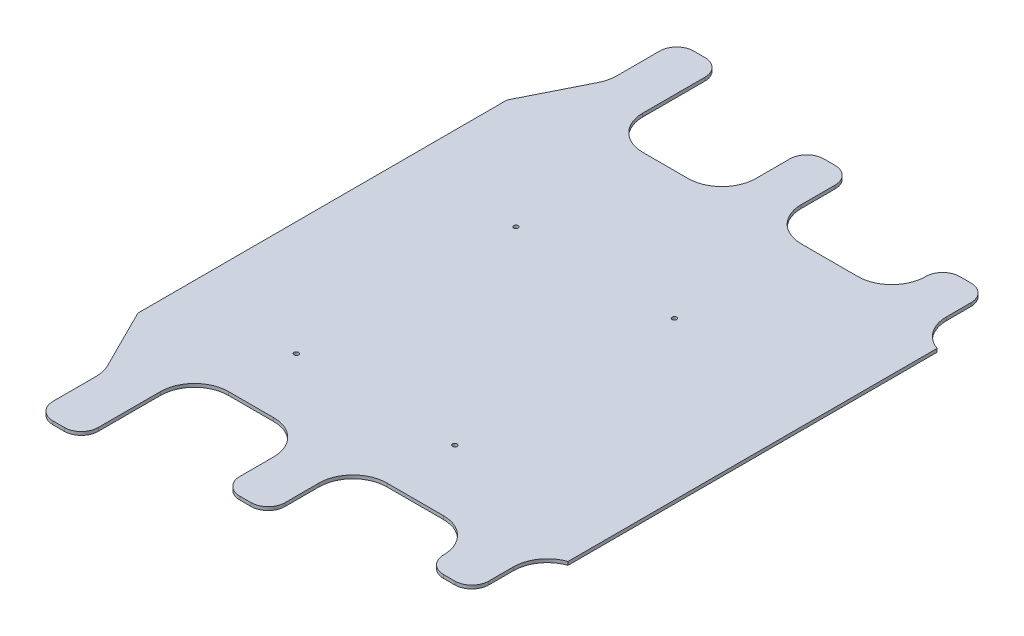
SolidWorks part; units mm, degrees
ref_plane "Front Plane" through (0, 0, 0) normal (0, 0, 1) x (1, 0, 0)
ref_plane "Top Plane" through (0, 0, 0) normal (0, 1, 0) x (1, 0, 0)
ref_plane "Right Plane" through (0, 0, 0) normal (1, 0, 0) x (0, 0, -1)
sketch "Sketch1" plane through (0, 0, 0) normal (0, 1, 0) x (1, 0, 0)
  line L1 (190, -163) -> (-190, -163)
  line L2 (190, -163) -> (190, 163)
  line L3 (190, 163) -> (-190, 163)
  line L4 (-190, -163) -> (-190, 163)
  line L5 (190, -163) -> (-190, 163) construction
  line L6 (190, 163) -> (-190, -163) construction
  point P0 (0, 0)
  dimension "D1" = 380
  dimension "D2" = 326
extrude "Boss-Extrude1" add sketch "Sketch1" along normal blind 3
sketch "Sketch2" plane through (0, 3, 0) normal (0, 1, 0) x (1, 0, 0)
  line L1 (67, -160) -> (67, 90) construction
  line L2 (67, 86) -> (-190, 86) construction
  circle A2 centre (51, 70) radius 2
  circle A4 centre (-89, 70) radius 2
  circle A5 centre (51, -124) radius 2
  circle A6 centre (-89, -124) radius 2
  dimension "D1" = 4
  dimension "D2" = 16
  dimension "D3" = 16
  dimension "D4" = 140
  dimension "D5" = 4
  dimension "D6" = 4
  dimension "D7" = 194
  dimension "D8" = 4
extrude "PCB Plate Holes" cut sketch "Sketch2" against normal up to surface (3 mm away) contours A4 | A2 | A5 | A6 up to face at (0, 0, 0)
sketch "Sketch3" plane through (0, 3, 0) normal (0, 1, 0) x (1, 0, 0)
  line L0 (190, 163) -> (-190, 163) construction
  line L5 (-190, 163) -> (-190, -163) construction
  line L7 (170, 163) -> (170, 228)
  line L11 (20, 163) -> (-20, 163)
  line L12 (130, 163) -> (170, 163)
  line L14 (170, 163) -> (170, 228)
  line L16 (190, -163) -> (190, 163) construction
  line L17 (170, 228) -> (130, 228)
  line L18 (130, 228) -> (130, 163)
  line L19 (-1.65, 0) -> (1.65, 0) construction
  line L20 (170, -228) -> (130, -228)
  line L21 (130, -228) -> (130, -163)
  line L22 (130, -163) -> (170, -163)
  line L23 (170, -163) -> (170, -228)
  line L24 (20, 163) -> (20, 258)
  line L25 (20, 258) -> (-20, 258)
  line L26 (-20, 163) -> (-20, 258)
  line L27 (-120, 163) -> (-160, 163)
  line L28 (-120, 163) -> (-120, 283)
  line L29 (-120, 283) -> (-160, 283)
  line L30 (-160, 163) -> (-160, 283)
  line L31 (-120, 183) -> (130, 183)
  line L32 (-120, -163) -> (-160, -163)
  line L33 (-160, -163) -> (-160, -283)
  line L34 (-120, -283) -> (-160, -283)
  line L35 (-120, -163) -> (-120, -283)
  line L36 (20, -163) -> (-20, -163)
  line L37 (-20, -163) -> (-20, -258)
  line L38 (20, -258) -> (-20, -258)
  line L39 (20, -163) -> (20, -258)
  line L40 (-120, -183) -> (130, -183)
  line L41 (-190, 163) -> (-160, 223)
  line L42 (-190, -163) -> (-160, -223)
  line L43 (170, 166) -> (190, 166)
  line L44 (190, 163) -> (190, 166)
  line L45 (-160, -283) -> (-160, -163)
  line L46 (190, -163) -> (190, -166)
  line L47 (170, -166) -> (190, -166)
  point P30 (130, 195.5)
  dimension "D2" = 20
  dimension "D3" = 3
  dimension "D1" = 20
  dimension "D4" = 65
  dimension "D5" = 30
  dimension "D6" = 40
  dimension "D7" = 110
  dimension "D8" = 40
  dimension "D9" = 40
  dimension "D10" = 120
  dimension "D11" = 95
extrude "Boss-Extrude2" add sketch "Sketch3" against normal up to surface (3 mm away) from surface at 0 up to face at (-89, 0, 126) starting at face at (-89, 3, 126)
sketch "Sketch5" plane through (0, 0, 0) normal (0, -1, 0) x (1, 0, 0)
  line L0 (190, -146.9564) -> (-165.4716, -212.0568)
  line L3 (-160, 272.0526) -> (170, 211.617)
  line L4 (-160, -241.5537) -> (170, -181.1181)
  line L6 (-160, -241.5537) -> (-160, -272.0526)
  line L8 (-160, -272.0526) -> (170, -211.617)
  line L12 (-140, 283) -> (-140, -283)
  line L15 (-190, -163) -> (-160, -223) construction
  line L16 (170, -163) -> (170, -228) construction
  line L19 (-120, 283) -> (-160, 283) construction
  line L26 (-120, -283) -> (-160, -283) construction
  line L32 (0, 258) -> (0, -258)
  line L34 (-160, 241.5537) -> (170, 181.1181)
  line L35 (20, 258) -> (-20, 258) construction
  line L36 (20, -258) -> (-20, -258) construction
  line L37 (150, -228) -> (150, 228)
  line L38 (170, 228) -> (130, 228) construction
  line L39 (-120, -183) -> (-120, -283) construction
  line L40 (190, 146.9564) -> (-165.4716, 212.0568)
  line L41 (170, 163) -> (170, 228) construction
  line L42 (170, -228) -> (130, -228) construction
  line L43 (-160, -223) -> (-160, -283) construction
  line L45 (1.65, 0) -> (-1.65, 0) construction
  line L48 (170, 211.617) -> (170, 181.1181)
  line L50 (-190, 0) -> (190, 0)
  line L51 (-190, -163) -> (-190, 163) construction
  line L52 (190, 163) -> (190, -163) construction
  dimension "D1" = 15
  dimension "D2" = 30
  dimension "D3" = 79.622
  dimension "D9" = 30
fillet "Fillet1" radius 30 12 edges at (130, 1.5, -183) (170, 1.5, -163) (20, 1.5, -183) (-20, 1.5, -183) (-120, 1.5, -183) (170, 1.5, 163) (20, 1.5, 183) (130, 1.5, 183) (-20, 1.5, 183) (-120, 1.5, 183) (-160, 1.5, -223) (-160, 1.5, 223)
fillet "Fillet2" radius 15 12 edges at (170, 1.5, 228) (130, 1.5, 228) (20, 1.5, 258) (-120, 1.5, 283) (-20, 1.5, 258) (170, 1.5, -228) (130, 1.5, -228) (20, 1.5, -258) (-20, 1.5, -258) (-120, 1.5, -283) (-160, 1.5, -283) (-160, 1.5, 283)
